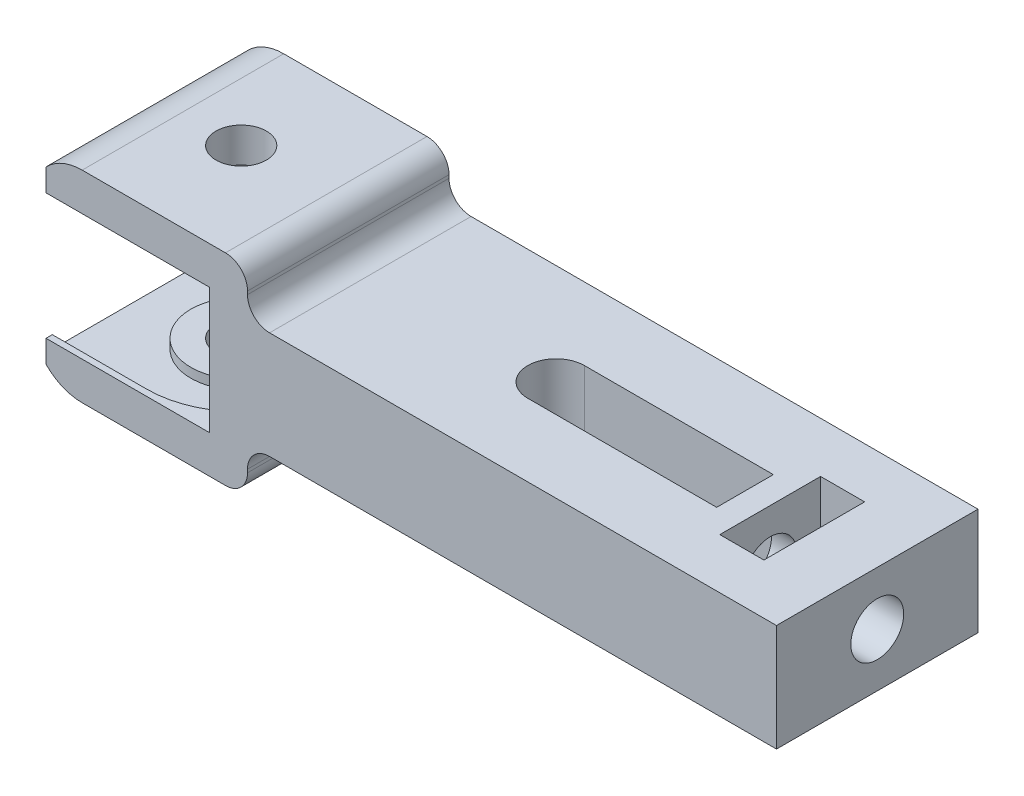
SolidWorks part; units mm, degrees
ref_plane "Front Plane" through (0, 0, 0) normal (0, 0, 1) x (1, 0, 0)
ref_plane "Top Plane" through (0, 0, 0) normal (0, 1, 0) x (1, 0, 0)
ref_plane "Right Plane" through (0, 0, 0) normal (1, 0, 0) x (0, 0, -1)
sketch "Sketch1" plane through (0, 0, 0) normal (0, 0, 1) x (1, 0, 0)
  line L0 (0, 0) -> (-42, 0)
  line L1 (-42, 0) -> (-42, 3.75)
  line L2 (-42, 3.75) -> (-59, 3.75)
  line L3 (-59, 3.75) -> (-59, 0.75)
  line L4 (-59, 0.75) -> (-45, 0.75)
  line L5 (-45, 0.75) -> (-45, -9.25)
  line L6 (0, 0) -> (0, -8.5)
  line L7 (0, -4.25) -> (-45, -4.25) construction
  line L8 (-59, -9.25) -> (-45, -9.25)
  line L9 (-59, -12.25) -> (-59, -9.25)
  line L10 (-42, -12.25) -> (-59, -12.25)
  line L11 (-42, -8.5) -> (-42, -12.25)
  line L12 (0, -8.5) -> (-42, -8.5)
  dimension "D1" = 59
  dimension "D2" = 14
  dimension "D3" = 4.25
  dimension "D4" = 5
  dimension "D5" = 3
  dimension "D6" = 17
extrude "Boss-Extrude1" add sketch "Sketch1" along normal blind 16
sketch "Sketch2" plane through (0, 0, 0) normal (0, 1, 0) x (1, 0, 0)
  line L0 (0, -8) -> (-42, -8) construction
  line L1 (0, -16) -> (0, 0) construction
  line L2 (-42, -16) -> (-42, 0) construction
  line L4 (-8.5, -4) -> (-5, -4)
  line L5 (-8.5, -4) -> (-8.5, -12)
  line L6 (-8.5, -12) -> (-5, -12)
  line L7 (-5, -4) -> (-5, -12)
  line L8 (-8.5, -4) -> (-5, -12) construction
  line L9 (-8.5, -12) -> (-5, -4) construction
  line L10 (-25.5, -10.25) -> (-10.5, -10.25)
  line L12 (-25.5, -5.75) -> (-10.5, -5.75)
  line L13 (-10.5, -10.25) -> (-10.5, -5.75)
  line L14 (-25.5, -10.25) -> (-10.5, -5.75) construction
  line L15 (-25.5, -5.75) -> (-10.5, -10.25) construction
  arc A0 (-25.5, -5.75) -> (-25.5, -10.25) centre (-25.5, -8) ccw
  point P6 (-6.75, -8)
  point P11 (-18, -8)
  dimension "D7" = 2.25
  dimension "D1" = 8
  dimension "D2" = 3.5
  dimension "D3" = 5
  dimension "D4" = 2
  dimension "D5" = 4.5
  dimension "D6" = 15
extrude "Cut-Extrude1" cut sketch "Sketch2" against normal through all
sketch "Sketch3" plane through (0, 0, 0) normal (1, 0, 0) x (0, 0, -1)
  line L0 (-8, 0) -> (-8, -8.5) construction
  line L1 (-16, 0) -> (0, 0) construction
  line L2 (-16, -8.5) -> (0, -8.5) construction
  circle A0 centre (-8, -4.25) radius 2.1
  dimension "D1" = 4.2
extrude "Cut-Extrude2" cut sketch "Sketch3" against normal up to surface (10.5 mm away) up to face at (-10.5, -4.25, 8)
fillet "Fillet1" radius 1.75 4 edges at (-42, -8.5, 8) (-42, 3.75, 8) (-42, 0, 8) (-42, -12.25, 8)
sketch "Sketch4" plane through (0, -9.25, 0) normal (0, 1, 0) x (1, 0, 0)
  line L0 (-59, -8) -> (-43.75, -8) construction
  line L1 (-59, -16) -> (-59, 0) construction
  line L2 (-43.75, 0) -> (-43.75, -16) construction
  circle A0 centre (-51.375, -8) radius 9
  dimension "D1" = 18
extrude "Cut-Extrude3" cut sketch "Sketch4" along normal up to surface (10 mm away) up to face at (-52, 0.75, 8)
sketch "Sketch5" plane through (0, 3.75, 0) normal (0, 1, 0) x (1, 0, 0)
  line L0 (-59, -8) -> (-43.75, -8) construction
  line L1 (-59, -16) -> (-59, 0) construction
  line L2 (-43.75, -16) -> (-43.75, 0) construction
  circle A0 centre (-50.5, -8) radius 2
  dimension "D1" = 4
  dimension "D2" = 8.5
extrude "Cut-Extrude4" cut sketch "Sketch5" against normal through all
fillet "Fillet2" radius 4 2 edges at (-59, -12.25, 8) (-59, 3.75, 8)
sketch "Sketch6" plane through (0, -9.25, 0) normal (0, 1, 0) x (1, 0, 0)
  line L0 (-50.5, -0.5) -> (-59, -0.5)
  line L1 (-59, -16) -> (-59, 0) construction
  line L2 (-50.5, -15.5) -> (-59, -15.5)
  line L3 (-59, -15.5) -> (-59, -0.5)
  arc A0 (-50.5, -15.5) -> (-50.5, -0.5) centre (-50.5, -8) ccw
  dimension "D1" = 15
extrude "Cut-Extrude5" cut sketch "Sketch6" against normal blind 1
sketch "Sketch7" plane through (0, -10.25, 0) normal (0, 1, 0) x (1, 0, 0)
  circle A0 centre (-50.5, -8) radius 4
  circle A1 centre (-50.5, -8) radius 2
  circle A2 centre (-50.5, -8) radius 2 construction
  dimension "D1" = 8
extrude "Boss-Extrude2" add sketch "Sketch7" along normal blind 0.75
ref_plane "Plane1" through (0, -4.25, 0) normal (0, 1, 0) x (1, 0, 0)
mirror "Mirror1" about plane through (0, -4.25, 0) normal (0, 1, 0) of "Boss-Extrude2", "Cut-Extrude5"
sketch "Sketch8" plane through (0, 0, 16) normal (0, 0, 1) x (1, 0, 0)
  line L0 (0, -4.25) -> (-60, -4.25) construction
  line L1 (0, -8.5) -> (0, 0) construction
  line L2 (8.8, -4.25) -> (-8.8, -4.25) construction
  line L3 (-43.75, 3.75) -> (-55.127, 3.75) construction
  line L4 (-62, -12.25) -> (-58, -12.25)
  line L5 (-62, -12.25) -> (-62, 3.75)
  line L6 (-62, 3.75) -> (-58, 3.75)
  line L7 (-58, -12.25) -> (-58, 3.75)
  line L8 (-62, -12.25) -> (-58, 3.75) construction
  line L9 (-62, 3.75) -> (-58, -12.25) construction
  dimension "D1" = 1
  dimension "D2" = 2
extrude "Cut-Extrude6" cut sketch "Sketch8" against normal through all
equation "\"X-ROD-SPACING\"=45"
equation "\"Y-ROD-SPACING\"=75"
equation "\"Z-ROD-SPACING\"=17.5"
equation "\"Y-BED-OFFSET\"=2"
equation "\"Y-BED-ROD-INSET\"=3.5"
equation "\"T-SLOT-NUT-FILLET-RADIUS\"=0.5"
equation "\"T-SLOT-SCREW-SHAFT-RADIUS\"=1.55"
equation "\"T-SLOT-SCREW-SHAFT-CUTOUT-LENGTH\"=11"
equation "\"T-SLOT-NUT-DEPTH\"=3.5"
equation "\"T-SLOT-NUT-WIDTH\"=2.85"
equation "\"T-SLOT-NUT-END-DISTANCE\"=8"
equation "\"ACRYLIC-THICKNESS\"=10"
equation "\"ACRYLIC-TAB-CUTOUT-SIZE\"=\"ACRYLIC-THICKNESS\"+\"ACRYLIC-TAB-TOLERANCE\"*2"
equation "\"ACRYLIC-TAB-WIDTH\"=\"ACRYLIC-THICKNESS\""
equation "\"ACRYLIC-M3-HOLE\"=2.9"
equation "\"SMOOTHROD-CAP-SCREW-DISTANCE\"=20"
equation "\"FRAME-WIDTH-INNER\"=370"
equation "\"NEMA17-HOLE-SPACING\"=31"
equation "\"NEMA17-CENTRAL-CUTOUT\"=22.5"
equation "\"Z-BRACKET-REACH\"=57"
equation "\"TOP-BRACKET-SPACING\"=40"
equation "\"SMOOTHROD-X-LENGTH\"=350"
equation "\"SMOOTHROD-Y-LENGTH\"=350"
equation "\"SMOOTHROD-Z-LENGTH\"=350"
equation "\"SMOOTHROD-TIGHTENING-HEADROOM\"=.25"
equation "\"LEADSCREW-Z-LENGTH\"=300"
equation "\"SCREW-HEAD-RADIUS\"=6"
equation "\"PRINTED-X-SMOOTHROD-DIAMETER\"=8.8"
equation "\"PRINTED-X-SMOOTHROD-CUTOUT\"=10"
equation "\"PRINTED-X-BASE-HEIGHT\"=10"
equation "\"PRINTED-LM8UU-CUTOUT-SIZE\"=15.5"
equation "\"PRINTED-LM8UU-CUTOUT-LENGTH\"=24.5"
equation "\"PRINTED-X-IDLER-HEIGHT\"=16"
equation "\"D1@Boss-Extrude1\"=\"PRINTED-X-IDLER-HEIGHT\""
